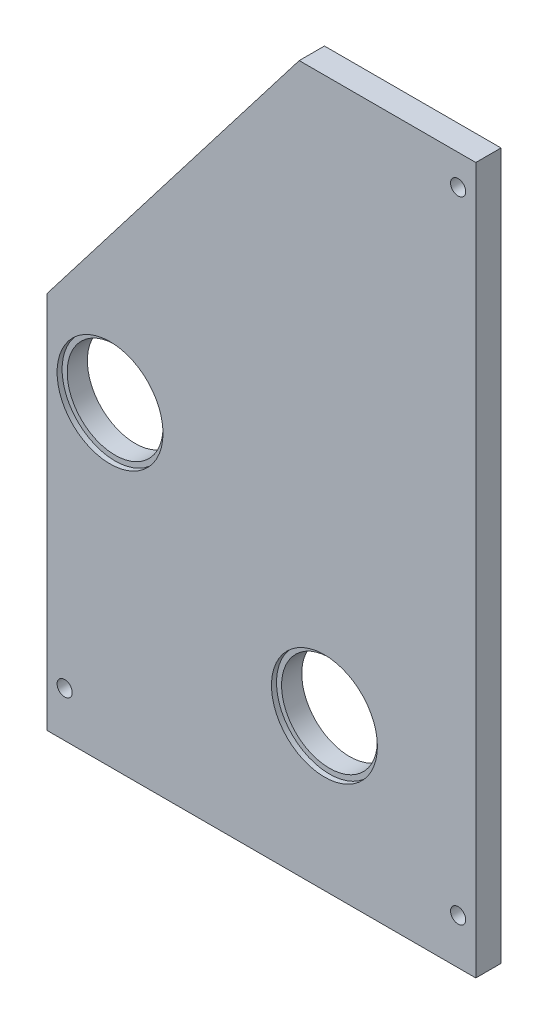
SolidWorks part; units mm, degrees
ref_plane "Front Plane" through (0, 0, 0) normal (0, 0, 1) x (1, 0, 0)
ref_plane "Top Plane" through (0, 0, 0) normal (0, 1, 0) x (1, 0, 0)
ref_plane "Right Plane" through (0, 0, 0) normal (1, 0, 0) x (0, 0, -1)
sketch "Sketch1" plane through (0, 0, 0) normal (0, 0, 1) x (1, 0, 0)
  line L1 (0, 0) -> (50, 0)
  line L2 (0, 0) -> (0, 50) construction
  line L3 (0, 50) -> (50, 50) construction
  line L4 (50, 0) -> (50, 50) construction
  line L5 (0, 0) -> (50, 50) construction
  line L6 (0, 50) -> (50, 0) construction
  line L11 (0, 0) -> (-25, 0)
  line L12 (-25, 0) -> (-25, 75)
  line L13 (-25, 75) -> (50, 75)
  line L14 (0, 50) -> (-25, 75) construction
  line L15 (50, 75) -> (50, 140)
  line L16 (-9.6132, 62.5) -> (-11.0566, 65) construction
  line L17 (-11.0566, 65) -> (-13.9434, 65) construction
  line L18 (-13.9434, 65) -> (-15.3868, 62.5) construction
  line L19 (-15.3868, 62.5) -> (-13.9434, 60) construction
  line L20 (-13.9434, 60) -> (-11.0566, 60) construction
  line L21 (-11.0566, 60) -> (-9.6132, 62.5) construction
  line L22 (53, 140) -> (53, 0) construction
  line L23 (-25, 75) -> (25, 140)
  line L24 (50, 140) -> (60, 140)
  line L25 (60, 140) -> (60, 0)
  line L26 (60, 0) -> (50, 0)
  line L27 (25, 140) -> (50, 140)
  circle A1 centre (-12.5, 62.5) radius 9.5
  circle A2 centre (-12.5, 62.5) radius 2.5 construction
  circle A3 centre (-12.5, 62.5) radius 5 construction
  circle A4 centre (56.5, 134) radius 1.5
  circle A5 centre (56.5, 9) radius 1.5
  circle A6 centre (-12.5, 62.5) radius 10.5
  circle A7 centre (-21.5, 9) radius 1.5
  point P4 (25, 25)
  point P6 (25, 25)
  dimension "D5" = 19
  dimension "D7" = 10
  dimension "D10" = 3
  dimension "D16" = 3
  dimension "D18" = 21
  dimension "D19" = 3
  dimension "D1" = 50
  dimension "D2" = 50
  dimension "D3" = 75
  dimension "D4" = 75
  dimension "D6" = 5
  dimension "D8" = 65
  dimension "D9" = 10
  dimension "D11" = 3
  dimension "D12" = 3.5
  dimension "D13" = 6
  dimension "D14" = 3.5
  dimension "D15" = 9
  dimension "D17" = 25
  dimension "D20" = 9
  dimension "D21" = 3.5
extrude "Boss-Extrude1" add sketch "Sketch1" along normal blind 5 contours L13 L12 L11 L1 L4 A1 | L26 L25 L24 L15 L4 | L13 L15 region at (22.6807, 42.9919, 0) region at (22.9167, 102.0833, 0)
extrude "Boss-Extrude2" add sketch "Sketch1<3>" along normal blind 4 contours A6 A1 region at (-22.703, 62.5, 0)
sketch "Sketch1<3>" plane through (0, 0, 0) normal (0, 0, 1) x (1, 0, 0) same geometry as "Sketch1"
sketch "Sketch3" plane through (0, 0, 5) normal (0, 0, 1) x (1, 0, 0)
  line L2 (16.3324, 12.1269) -> (-26.1676, 44.6269)
  line L3 (1.1676, 80.3731) -> (43.6676, 47.8731)
  line L4 (60, 0) -> (-25, 0) construction
  line L5 (60, 140) -> (60, 0) construction
  circle A0 centre (30, 30) radius 16 construction
  circle A3 centre (-12.5, 62.5) radius 22.5
  circle A4 centre (30, 30) radius 22.5
  circle A5 centre (30, 30) radius 10.5
  circle A6 centre (30, 30) radius 9.5
  dimension "D1" = 32
  dimension "D2" = 45
  dimension "D3" = 45
  dimension "D6" = 21
  dimension "D7" = 19
  dimension "D4" = 30
  dimension "D5" = 30
extrude "Cut-Extrude2" cut sketch "Sketch3<3>" against normal up to surface (5 mm away) contours A6 region at (30, 30, 5) up to face at (19, 71, 0)
sketch "Sketch3<3>" plane through (0, 0, 5) normal (0, 0, 1) x (1, 0, 0) same geometry as "Sketch3"
extrude "Cut-Extrude3" cut sketch "Sketch3" against normal blind 1 contours A5 A6 region at (19.797, 30, 5)
